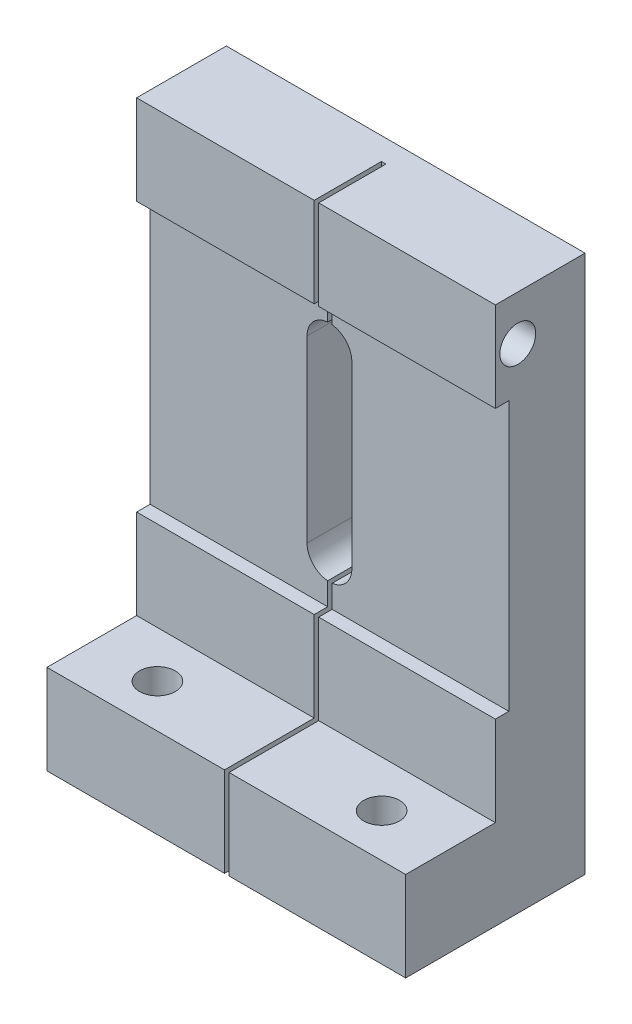
SolidWorks part; units mm, degrees
ref_plane "Front Plane" through (0, 0, 0) normal (0, 0, 1) x (1, 0, 0)
ref_plane "Top Plane" through (0, 0, 0) normal (0, 1, 0) x (1, 0, 0)
ref_plane "Right Plane" through (0, 0, 0) normal (1, 0, 0) x (0, 0, -1)
sketch "Sketch1" plane through (0, 0, 0) normal (0, 0, 1) x (1, 0, 0)
  line L1 (0, 0) -> (-40, 0)
  line L2 (0, 0) -> (0, -60)
  line L3 (0, -60) -> (-40, -60)
  line L4 (-40, 0) -> (-40, -60)
  dimension "D1" = 40
  dimension "D2" = 60
extrude "Boss-Extrude1" add sketch "Sketch1" along normal blind 10
sketch "Sketch2" plane through (0, 0, 10) normal (0, 0, 1) x (1, 0, 0)
  line L0 (-20, -15) -> (-20, -35) construction
  line L1 (-17.5, -15) -> (-17.5, -35)
  line L2 (-22.5, -15) -> (-22.5, -35)
  line L3 (0, -60) -> (0, 0) construction
  line L4 (-40, -60) -> (0, -60) construction
  arc A0 (-17.5, -15) -> (-22.5, -15) centre (-20, -15) ccw
  arc A1 (-22.5, -35) -> (-17.5, -35) centre (-20, -35) ccw
  point P2 (-20, -25)
  dimension "D1" = 5
  dimension "D2" = 20
  dimension "D3" = 20
  dimension "D4" = 35
extrude "Cut-Extrude1" cut sketch "Sketch2" against normal through all
sketch "Sketch5" plane through (0, 0, 0) normal (1, 0, 0) x (0, 0, -1)
  line L0 (-8.5, -10) -> (-10, -10)
  line L1 (-10, -60) -> (-10, 0) construction
  line L2 (-8.5, -10) -> (-8.5, -40)
  line L3 (-10, -60) -> (0, -60) construction
  line L4 (-8.5, -40) -> (-10, -40)
  line L7 (-10, -10) -> (-10, -40)
  dimension "D1" = 1.5
  dimension "D4" = 30
  dimension "D5" = 20
extrude "Cut-Extrude4" cut sketch "Sketch5" against normal through all
sketch "Sketch6" plane through (0, 0, 10) normal (0, 0, 1) x (1, 0, 0)
  line L0 (-40, -40) -> (-40, -60) construction
  line L1 (0, -60) -> (-40, -60)
  line L2 (0, -60) -> (0, -50)
  line L3 (0, -50) -> (-40, -50)
  line L4 (-40, -60) -> (-40, -50)
  dimension "D1" = 10
extrude "Boss-Extrude2" add sketch "Sketch6" along normal blind 10
sketch "Sketch7" plane through (0, -50, 0) normal (0, 1, 0) x (1, 0, 0)
  line L3 (-40, -20) -> (-40, -10) construction
  circle A0 centre (-7.5, -15.1829) radius 2
  circle A1 centre (-32.5, -15.1829) radius 2
  dimension "D1" = 4
  dimension "D2" = 4
  dimension "D3" = 7.5
  dimension "D5" = 25
extrude "Cut-Extrude5" cut sketch "Sketch7" against normal blind 40
sketch "Sketch8" plane through (0, 0, 0) normal (0, 1, 0) x (1, 0, 0)
  line L2 (-20.2, -20) -> (-19.7, -20)
  line L5 (-20.2, -20) -> (-20.2, -2.5)
  line L7 (0, -20) -> (-40, -20) construction
  line L9 (-20.2, -2.5) -> (-19.7, -2.5)
  line L10 (-19.7, -20) -> (-19.7, -2.5)
  line L11 (-22.5, 0) -> (-22.5, -8.5) construction
  dimension "D1" = 0.5
  dimension "D2" = 2.3
  dimension "D3" = 17.5
extrude "Cut-Extrude7" cut sketch "Sketch8" against normal up to surface (60 mm away) up to face at (-32.5, -60, 17.1829)
sketch "Sketch9" plane through (0, -60, 0) normal (0, -1, 0) x (1, 0, 0)
  line L3 (0, 20) -> (0, 0) construction
  line L5 (-40, 8.5) -> (-20.2, 8.5) construction
  circle A0 centre (-32.5, 6.5) radius 2
  circle A1 centre (-7.5, 6.5) radius 2
  dimension "D1" = 4
  dimension "D3" = 7.5
  dimension "D4" = 4
  dimension "D2" = 25
extrude "Cut-Extrude9" cut sketch "Sketch9" against normal blind 15
sketch "Sketch10" plane through (0, 0, 0) normal (1, 0, 0) x (0, 0, -1)
  line L1 (-10, 0) -> (0, 0) construction
  line L2 (-10, -10) -> (-10, 0) construction
  circle A0 centre (-7.5, -5) radius 2
  dimension "D1" = 4
  dimension "D2" = 5
  dimension "D3" = 2.5
extrude "Cut-Extrude10" cut sketch "Sketch10" against normal blind 30
